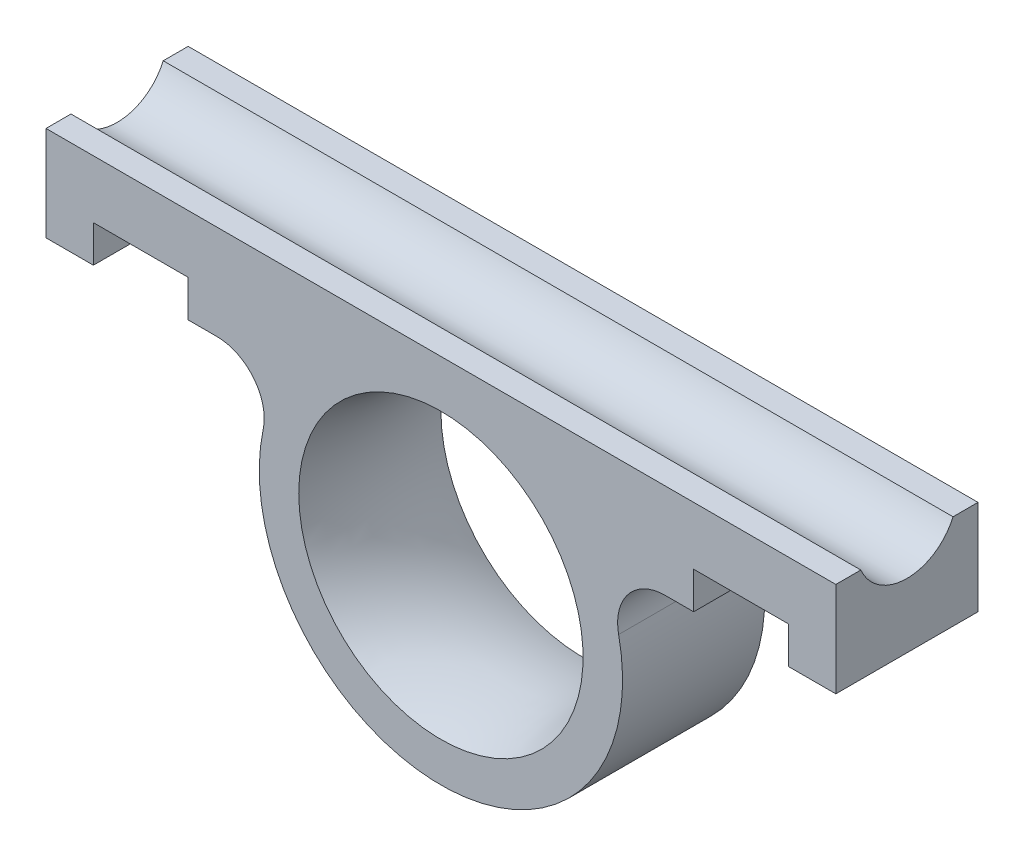
SolidWorks part; units mm, degrees
ref_plane "Front Plane" through (0, 0, 0) normal (0, 0, 1) x (1, 0, 0)
ref_plane "Top Plane" through (0, 0, 0) normal (0, 1, 0) x (1, 0, 0)
ref_plane "Right Plane" through (0, 0, 0) normal (1, 0, 0) x (0, 0, -1)
sketch "Sketch2" plane through (0, 0, 0) normal (0, 0, 1) x (1, 0, 0)
  line L0 (-25, 8.825) -> (25, 8.825) construction
  line L1 (-25, 12) -> (25, 12)
  line L2 (-25, 12) -> (-25, 6)
  line L3 (-25, 6) -> (-22, 6)
  line L4 (25, 12) -> (25, 6)
  line L5 (-22, 6) -> (-22, 7)
  line L6 (-22, 7) -> (-16, 7)
  line L7 (-16, 7) -> (-16, 6)
  line L8 (16, 6) -> (16, 7)
  line L9 (16, 7) -> (22, 7)
  line L10 (22, 7) -> (22, 6)
  line L11 (-16, 6) -> (-14.1863, 6)
  line L12 (22, 6) -> (25, 6)
  line L13 (14.1863, 6) -> (16, 6)
  line L14 (0, 12) -> (0, 0) construction
  circle A0 centre (0, 0) radius 8.25
  arc A1 (-11.2512, 2.3793) -> (11.2512, 2.3793) centre (0, 0) ccw
  arc A2 (14.1863, 6) -> (11.2512, 2.3793) centre (14.1863, 3) ccw
  arc A3 (-11.2512, 2.3793) -> (-14.1863, 6) centre (-14.1863, 3) ccw
  dimension "D1" = 16.5
  dimension "D2" = 23
  dimension "D10" = 3
  dimension "D3" = 3.175
  dimension "D4" = 12
  dimension "D5" = 6
  dimension "D6" = 1
  dimension "D7" = 3
  dimension "D8" = 6
  dimension "D9" = 50
extrude "Boss-Extrude1" add sketch "Sketch2" along normal blind 9
sketch "Sketch3" plane through (25, 0, 0) normal (1, 0, 0) x (0, 0, -1)
  line L1 (-4.5, 13.25) -> (-4.5, 12) construction
  line L2 (-9, 12) -> (0, 12) construction
  circle A0 centre (-4.5, 13.25) radius 3.175
  dimension "D1" = 6.35
  dimension "D2" = 1.25
extrude "Cut-Extrude1" cut sketch "Sketch3" against normal through all
sketch "Sketch4" plane through (-22, 0, 0) normal (1, 0, 0) x (0, 0, -1)
  line L0 (-9, 7) -> (0, 7) construction
  line L1 (-4.5, 15.25) -> (-4.5, 13.25) construction
  circle A0 centre (-4.5, 15.25) radius 8.25
  dimension "D1" = 2
extrude "Cut-Extrude2" cut sketch "Sketch4" along normal up to surface (6 mm away) flip side to cut up to face at (-16, 6.5, 4.5)
sketch "Sketch5" plane through (16, 0, 0) normal (-1, 0, 0) x (0, 0, 1)
  line L3 (0, 8.3353) -> (0, 6)
  line L4 (0, 6) -> (9, 6)
  line L5 (9, 6) -> (9, 8.3353)
  line L6 (0, 8.3353) -> (0, 6)
  line L7 (0, 6) -> (9, 6)
  line L8 (9, 6) -> (9, 8.3353)
  arc A1 (0, 8.3353) -> (9, 8.3353) centre (4.5, 15.25) ccw
  arc A2 (0, 8.3353) -> (9, 8.3353) centre (4.5, 15.25) ccw
  dimension "D1" = 0
extrude "Cut-Extrude3" cut sketch "Sketch5" against normal up to surface (6 mm away) up to face at (22, 6.5, 4.5)
sketch "Sketch6" plane through (0, 0, 0) normal (1, 0, 0) x (0, 0, -1)
  line L0 (-9, 8.25) -> (-9, -8.25) construction
  line L1 (-9, 8.25) -> (-9, -8.25) construction
  line L2 (0, -8.25) -> (0, 8.25) construction
  line L3 (0, -8.25) -> (0, 8.25) construction
  line L4 (-9, 8.25) -> (0, 8.25) construction
  line L5 (-4.5, 22.125) -> (-4.5, 13.25) construction
  line L6 (-9, 9) -> (-9, 0)
  line L7 (-9, 0) -> (0, 0)
  line L8 (0, 0) -> (0, 9)
  line L9 (0, 6) -> (0, 12) construction
  line L10 (-9, 6) -> (-9, 12) construction
  line L11 (-9, 0) -> (-19.7115, 0) construction
  arc A0 (-9, 9) -> (0, 9) centre (-4.5, 22.125) ccw
  dimension "D1" = 9
revolve "Cut-Revolve1" cut sketch "Sketch6" angle 360 about L11
ref_axis "Axis1" through (0, 0, 20.6971) along (0, 0, -1)
